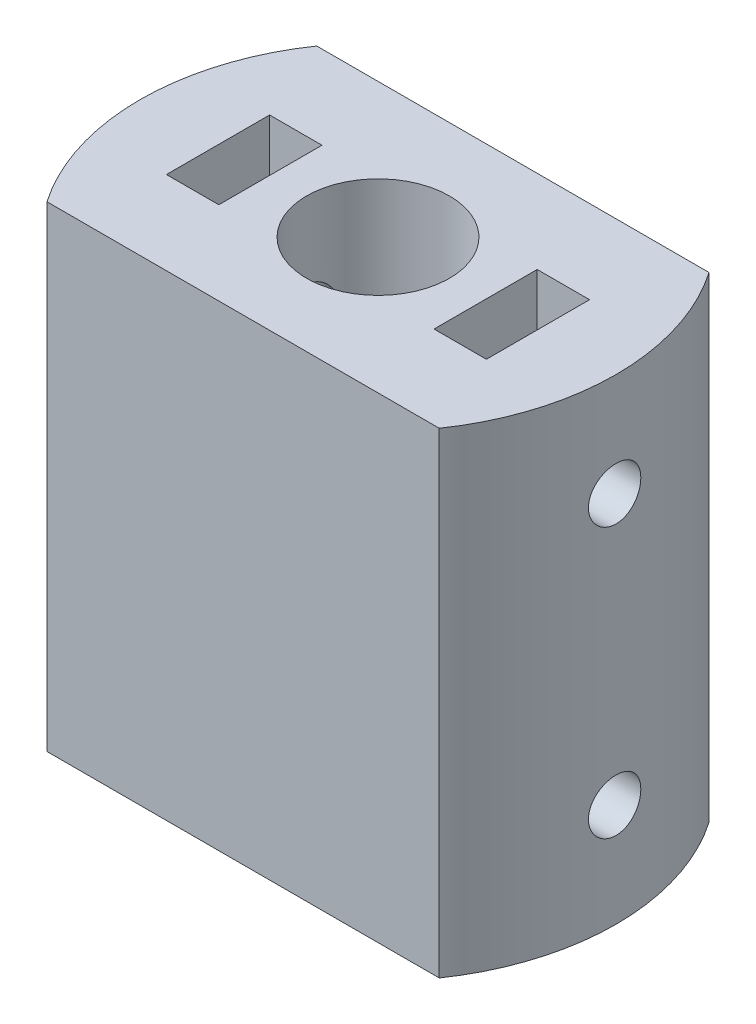
SolidWorks part; units mm, degrees
ref_plane "Plano frontal" through (0, 0, 0) normal (0, 0, 1) x (1, 0, 0)
ref_plane "Plano superior" through (0, 0, 0) normal (0, 1, 0) x (1, 0, 0)
ref_plane "Plano direito" through (0, 0, 0) normal (1, 0, 0) x (0, 0, -1)
sketch "Esboço1" plane through (0, 0, 0) normal (0, 0, 1) x (1, 0, 0)
  line L0 (4.5, 30) -> (15, 30)
  line L1 (15, 30) -> (15, 0)
  line L2 (15, 0) -> (3.25, 0)
  line L3 (3.25, 0) -> (3.25, 15)
  line L4 (3.25, 15) -> (4.5, 15)
  line L5 (4.5, 15) -> (4.5, 30)
  line L6 (0, 0) -> (0, 76.1392) construction
  point P9 (10.2439, 14.8036)
  point P10 (15, 15)
  dimension "D1" = 9
  dimension "D2" = 30
  dimension "D3" = 30
  dimension "D4" = 6.5
revolve "Revolução1" add sketch "Esboço1" angle 360 about L6
sketch "Esboço2" plane through (0, 0, 0) normal (0, -1, 0) x (1, 0, 0)
  line L0 (15, 0) -> (3.25, 0) construction
  line L1 (0, 9.1628) -> (0, -11.3333) construction
  line L2 (6.7808, 3.25) -> (10.0808, 3.25)
  line L3 (6.7808, 3.25) -> (6.7808, -3.25)
  line L4 (6.7808, -3.25) -> (10.0808, -3.25)
  line L5 (10.0808, 3.25) -> (10.0808, -3.25)
  line L6 (6.7808, 3.25) -> (10.0808, -3.25) construction
  line L7 (6.7808, -3.25) -> (10.0808, 3.25) construction
  line L8 (-6.7808, -3.25) -> (-10.0808, 3.25) construction
  line L9 (-6.7808, 3.25) -> (-10.0808, -3.25) construction
  line L10 (-15, 0) -> (-3.25, 0) construction
  line L11 (-10.0808, 3.25) -> (-10.0808, -3.25)
  line L12 (-6.7808, -3.25) -> (-10.0808, -3.25)
  line L13 (-6.7808, 3.25) -> (-6.7808, -3.25)
  line L14 (-6.7808, 3.25) -> (-10.0808, 3.25)
  circle A0 centre (0, 0) radius 15 construction
  circle A1 centre (0, 0) radius 3.25 construction
  point P7 (8.4308, 0)
  point P21 (-8.4308, 0)
  dimension "D1" = 6.5
  dimension "D2" = 3.3
extrude "Corte-extrusão1" cut sketch "Esboço2" against normal blind 13
extrude "Corte-extrusão2" cut sketch "Esboço2<2>" along normal blind 13 from surface starting at face at (0, 30, -4.5)
sketch "Esboço2<2>" plane through (0, 0, 0) normal (0, -1, 0) x (1, 0, 0) same geometry as "Esboço2"
sketch "Esboço3" plane through (6.7808, 0, 0) normal (1, 0, 0) x (0, 0, -1)
  line L0 (0, 30) -> (0, 17) construction
  line L1 (-3.25, 30) -> (3.25, 30) construction
  line L2 (-3.25, 17) -> (3.25, 17) construction
  line L3 (0, 0) -> (0, 13) construction
  line L4 (3.25, 0) -> (-3.25, 0) construction
  line L5 (3.25, 13) -> (-3.25, 13) construction
  circle A0 centre (0, 23.5) radius 1.65
  circle A1 centre (0, 6.5) radius 1.65
  dimension "D1" = 3.3
extrude "Corte-extrusão4" cut sketch "Esboço3" against normal through all from offset 15
sketch "Esboço4" plane through (0, 0, 0) normal (0, -1, 0) x (1, 0, 0)
  line L1 (-19.8436, 8.5) -> (19.8436, 8.5)
  line L2 (-19.8436, 8.5) -> (-19.8436, -8.5)
  line L3 (-19.8436, -8.5) -> (19.8436, -8.5)
  line L4 (19.8436, 8.5) -> (19.8436, -8.5)
  line L5 (-19.8436, 8.5) -> (19.8436, -8.5) construction
  line L6 (-19.8436, -8.5) -> (19.8436, 8.5) construction
  point P0 (0, 0)
  dimension "D1" = 17
extrude "Corte-Extrusão-Fina1" cut sketch "Esboço4" against normal blind 33 thin thin type one direction wall 10
